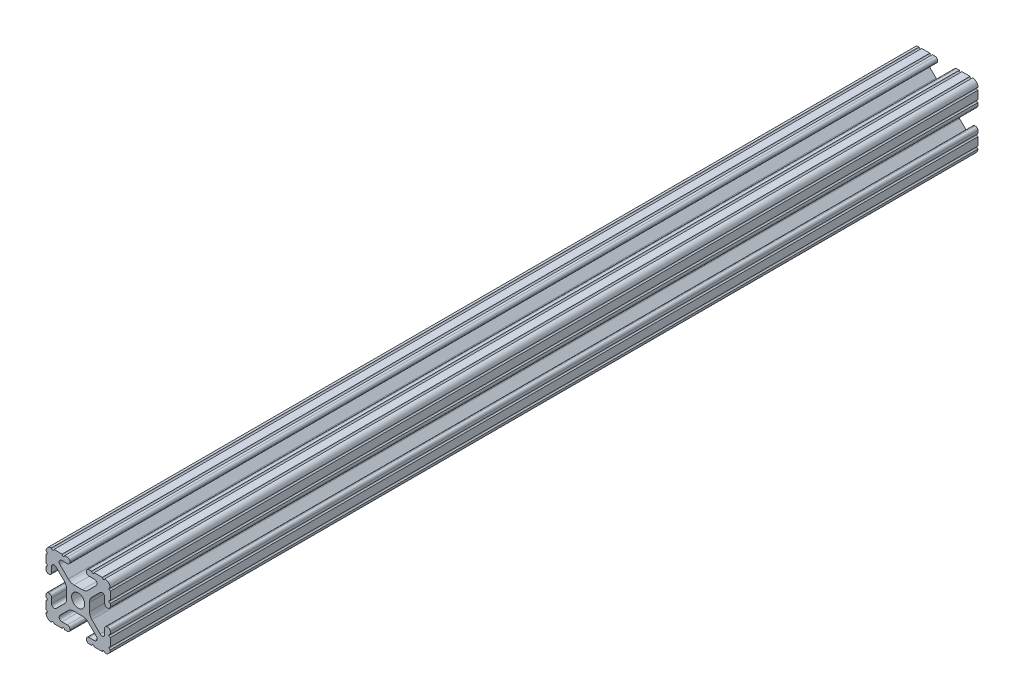
SolidWorks part; units mm, degrees
ref_plane "Front Plane" through (0, 0, 0) normal (0, 0, 1) x (1, 0, 0)
ref_plane "Top Plane" through (0, 0, 0) normal (0, 1, 0) x (1, 0, 0)
ref_plane "Right Plane" through (0, 0, 0) normal (1, 0, 0) x (0, 0, -1)
sketch "Sketch1" plane through (0, 0, 0) normal (0, 0, 1) x (1, 0, 0)
  line L88 (-7.1797, -8.6452) -> (-3.9523, -5.4237)
  line L89 (-1.7093, -4.4958) -> (1.7093, -4.4958)
  line L90 (3.9523, -5.4237) -> (7.1797, -8.6452)
  line L91 (6.4164, -10.4902) -> (4.2875, -10.4902)
  line L92 (3.2385, -11.5392) -> (3.2385, -11.651)
  line L93 (4.2875, -12.7) -> (5.3171, -12.7)
  line L94 (6.3331, -12.7) -> (9.5504, -12.7)
  line L95 (12.7, -9.5504) -> (12.7, -6.3331)
  line L96 (12.7, -5.3171) -> (12.7, -4.2875)
  line L97 (11.651, -3.2385) -> (11.5392, -3.2385)
  line L98 (10.4902, -4.2875) -> (10.4902, -6.4021)
  line L99 (8.7371, -7.1294) -> (5.441, -3.8408)
  line L100 (4.5085, -1.5932) -> (4.5085, 1.5932)
  line L101 (5.441, 3.8408) -> (8.7371, 7.1294)
  line L102 (10.4902, 6.4021) -> (10.4902, 4.2875)
  line L103 (11.5392, 3.2385) -> (11.651, 3.2385)
  line L104 (12.7, 4.2875) -> (12.7, 5.3171)
  line L105 (12.7, 6.3331) -> (12.7, 9.5504)
  line L106 (9.5504, 12.7) -> (6.3331, 12.7)
  line L107 (5.3171, 12.7) -> (4.2875, 12.7)
  line L108 (3.2385, 11.651) -> (3.2385, 11.5392)
  line L109 (4.2875, 10.4902) -> (6.4768, 10.4902)
  line L110 (7.207, 8.7244) -> (3.8983, 5.4232)
  line L111 (1.6558, 4.4958) -> (-1.6558, 4.4958)
  line L112 (-3.8983, 5.4232) -> (-7.207, 8.7244)
  line L113 (-6.4768, 10.4902) -> (-4.2875, 10.4902)
  line L114 (-3.2385, 11.5392) -> (-3.2385, 11.651)
  line L115 (-4.2875, 12.7) -> (-5.3171, 12.7)
  line L116 (-6.3331, 12.7) -> (-9.5504, 12.7)
  line L117 (-12.7, 9.5504) -> (-12.7, 6.3331)
  line L118 (-12.7, 5.3171) -> (-12.7, 4.2875)
  line L119 (-11.651, 3.2385) -> (-11.5392, 3.2385)
  line L120 (-10.4902, 4.2875) -> (-10.4902, 6.4021)
  line L121 (-8.7371, 7.1294) -> (-5.441, 3.8408)
  line L122 (-4.5085, 1.5932) -> (-4.5085, -1.5932)
  line L123 (-5.441, -3.8408) -> (-8.7371, -7.1294)
  line L124 (-10.4902, -6.4021) -> (-10.4902, -4.2875)
  line L125 (-11.5392, -3.2385) -> (-11.651, -3.2385)
  line L126 (-12.7, -4.2875) -> (-12.7, -5.3171)
  line L127 (-12.7, -6.3331) -> (-12.7, -9.5504)
  line L128 (-9.5504, -12.7) -> (-6.3331, -12.7)
  line L129 (-5.3171, -12.7) -> (-4.2875, -12.7)
  line L130 (-3.2385, -11.651) -> (-3.2385, -11.5392)
  line L131 (-4.2875, -10.4902) -> (-6.4164, -10.4902)
  circle A1 centre (0, 0) radius 2.6035
  arc A104 (-7.1797, -8.6452) -> (-6.4164, -10.4902) centre (-6.4164, -9.4098) ccw
  arc A105 (-1.7093, -4.4958) -> (-3.9523, -5.4237) centre (-1.7093, -7.6708) ccw
  arc A106 (3.9523, -5.4237) -> (1.7093, -4.4958) centre (1.7093, -7.6708) ccw
  arc A107 (6.4164, -10.4902) -> (7.1797, -8.6452) centre (6.4164, -9.4098) ccw
  arc A108 (4.2875, -10.4902) -> (3.2385, -11.5392) centre (4.2875, -11.5392) ccw
  arc A109 (3.2385, -11.651) -> (4.2875, -12.7) centre (4.2875, -11.651) ccw
  arc A110 (6.3331, -12.7) -> (5.3171, -12.7) centre (5.8251, -12.7) ccw
  arc A111 (10.5664, -12.6998) -> (9.5504, -12.7) centre (10.0584, -12.7) ccw
  arc A112 (10.5664, -12.6998) -> (12.6998, -10.5664) centre (10.5918, -10.5918) ccw
  arc A113 (12.7, -9.5504) -> (12.6998, -10.5664) centre (12.7, -10.0584) ccw
  arc A114 (12.7, -5.3171) -> (12.7, -6.3331) centre (12.7, -5.8251) ccw
  arc A115 (12.7, -4.2875) -> (11.651, -3.2385) centre (11.651, -4.2875) ccw
  arc A116 (11.5392, -3.2385) -> (10.4902, -4.2875) centre (11.5392, -4.2875) ccw
  arc A117 (8.7371, -7.1294) -> (10.4902, -6.4021) centre (9.4628, -6.4021) ccw
  arc A118 (4.5085, -1.5932) -> (5.441, -3.8408) centre (7.6835, -1.5932) ccw
  arc A119 (5.441, 3.8408) -> (4.5085, 1.5932) centre (7.6835, 1.5932) ccw
  arc A120 (10.4902, 6.4021) -> (8.7371, 7.1294) centre (9.4628, 6.4021) ccw
  arc A121 (10.4902, 4.2875) -> (11.5392, 3.2385) centre (11.5392, 4.2875) ccw
  arc A122 (11.651, 3.2385) -> (12.7, 4.2875) centre (11.651, 4.2875) ccw
  arc A123 (12.7, 6.3331) -> (12.7, 5.3171) centre (12.7, 5.8251) ccw
  arc A124 (12.6998, 10.5664) -> (12.7, 9.5504) centre (12.7, 10.0584) ccw
  arc A125 (12.6998, 10.5664) -> (10.5664, 12.6998) centre (10.5918, 10.5918) ccw
  arc A126 (9.5504, 12.7) -> (10.5664, 12.6998) centre (10.0584, 12.7) ccw
  arc A127 (5.3171, 12.7) -> (6.3331, 12.7) centre (5.8251, 12.7) ccw
  arc A128 (4.2875, 12.7) -> (3.2385, 11.651) centre (4.2875, 11.651) ccw
  arc A129 (3.2385, 11.5392) -> (4.2875, 10.4902) centre (4.2875, 11.5392) ccw
  arc A130 (7.207, 8.7244) -> (6.4768, 10.4902) centre (6.4768, 9.4563) ccw
  arc A131 (1.6558, 4.4958) -> (3.8983, 5.4232) centre (1.6558, 7.6708) ccw
  arc A132 (-3.8983, 5.4232) -> (-1.6558, 4.4958) centre (-1.6558, 7.6708) ccw
  arc A133 (-6.4768, 10.4902) -> (-7.207, 8.7244) centre (-6.4768, 9.4563) ccw
  arc A134 (-4.2875, 10.4902) -> (-3.2385, 11.5392) centre (-4.2875, 11.5392) ccw
  arc A135 (-3.2385, 11.651) -> (-4.2875, 12.7) centre (-4.2875, 11.651) ccw
  arc A136 (-6.3331, 12.7) -> (-5.3171, 12.7) centre (-5.8251, 12.7) ccw
  arc A137 (-10.5664, 12.6998) -> (-9.5504, 12.7) centre (-10.0584, 12.7) ccw
  arc A138 (-10.5664, 12.6998) -> (-12.6998, 10.5664) centre (-10.5918, 10.5918) ccw
  arc A139 (-12.7, 9.5504) -> (-12.6998, 10.5664) centre (-12.7, 10.0584) ccw
  arc A140 (-12.7, 5.3171) -> (-12.7, 6.3331) centre (-12.7, 5.8251) ccw
  arc A141 (-12.7, 4.2875) -> (-11.651, 3.2385) centre (-11.651, 4.2875) ccw
  arc A142 (-11.5392, 3.2385) -> (-10.4902, 4.2875) centre (-11.5392, 4.2875) ccw
  arc A143 (-8.7371, 7.1294) -> (-10.4902, 6.4021) centre (-9.4628, 6.4021) ccw
  arc A144 (-4.5085, 1.5932) -> (-5.441, 3.8408) centre (-7.6835, 1.5932) ccw
  arc A145 (-5.441, -3.8408) -> (-4.5085, -1.5932) centre (-7.6835, -1.5932) ccw
  arc A146 (-10.4902, -6.4021) -> (-8.7371, -7.1294) centre (-9.4628, -6.4021) ccw
  arc A147 (-10.4902, -4.2875) -> (-11.5392, -3.2385) centre (-11.5392, -4.2875) ccw
  arc A148 (-11.651, -3.2385) -> (-12.7, -4.2875) centre (-11.651, -4.2875) ccw
  arc A149 (-12.7, -6.3331) -> (-12.7, -5.3171) centre (-12.7, -5.8251) ccw
  arc A150 (-12.6998, -10.5664) -> (-12.7, -9.5504) centre (-12.7, -10.0584) ccw
  arc A151 (-12.6998, -10.5664) -> (-10.5664, -12.6998) centre (-10.5918, -10.5918) ccw
  arc A152 (-9.5504, -12.7) -> (-10.5664, -12.6998) centre (-10.0584, -12.7) ccw
  arc A153 (-5.3171, -12.7) -> (-6.3331, -12.7) centre (-5.8251, -12.7) ccw
  arc A154 (-4.2875, -12.7) -> (-3.2385, -11.651) centre (-4.2875, -11.651) ccw
  arc A155 (-3.2385, -11.5392) -> (-4.2875, -10.4902) centre (-4.2875, -11.5392) ccw
extrude "Boss-Extrude1" add sketch "Sketch1" along normal mid plane 431.8
ref_plane "Plane1" through (0, 0, 0) normal (0, 1, 0) x (1, 0, 0)
ref_plane "Plane2" through (0, 0, 0) normal (-1, 0, 0) x (0, 0, 1)
sketch "Sketch2" plane through (0, 0, -215.9) normal (0, 0, -1) x (-1, 0, 0)
  line L44 (6.4164, -10.4902) -> (4.2875, -10.4902)
  line L45 (3.2385, -11.5392) -> (3.2385, -11.651)
  line L46 (4.2875, -12.7) -> (5.3171, -12.7)
  line L47 (6.3331, -12.7) -> (9.5504, -12.7)
  line L48 (12.7, -9.5504) -> (12.7, -6.3331)
  line L49 (12.7, -5.3171) -> (12.7, -4.2875)
  line L50 (11.651, -3.2385) -> (11.5392, -3.2385)
  line L51 (10.4902, -4.2875) -> (10.4902, -6.4021)
  line L52 (8.7371, -7.1294) -> (5.441, -3.8408)
  line L53 (4.5085, -1.5932) -> (4.5085, 1.5932)
  line L54 (5.441, 3.8408) -> (8.7371, 7.1294)
  line L55 (10.4902, 6.4021) -> (10.4902, 4.2875)
  line L56 (11.5392, 3.2385) -> (11.651, 3.2385)
  line L57 (12.7, 4.2875) -> (12.7, 5.3171)
  line L58 (12.7, 6.3331) -> (12.7, 9.5504)
  line L59 (9.5504, 12.7) -> (6.3331, 12.7)
  line L60 (5.3171, 12.7) -> (4.2875, 12.7)
  line L61 (3.2385, 11.651) -> (3.2385, 11.5392)
  line L62 (4.2875, 10.4902) -> (6.4768, 10.4902)
  line L63 (7.207, 8.7244) -> (3.8983, 5.4232)
  line L64 (1.6558, 4.4958) -> (-1.6558, 4.4958)
  line L65 (-3.8983, 5.4232) -> (-7.207, 8.7244)
  line L66 (-6.4768, 10.4902) -> (-4.2875, 10.4902)
  line L67 (-3.2385, 11.5392) -> (-3.2385, 11.651)
  line L68 (-4.2875, 12.7) -> (-5.3171, 12.7)
  line L69 (-6.3331, 12.7) -> (-9.5504, 12.7)
  line L70 (-12.7, 9.5504) -> (-12.7, 6.3331)
  line L71 (-12.7, 5.3171) -> (-12.7, 4.2875)
  line L72 (-11.651, 3.2385) -> (-11.5392, 3.2385)
  line L73 (-10.4902, 4.2875) -> (-10.4902, 6.4021)
  line L74 (-8.7371, 7.1294) -> (-5.441, 3.8408)
  line L75 (-4.5085, 1.5932) -> (-4.5085, -1.5932)
  line L76 (-5.441, -3.8408) -> (-8.7371, -7.1294)
  line L77 (-10.4902, -6.4021) -> (-10.4902, -4.2875)
  line L78 (-11.5392, -3.2385) -> (-11.651, -3.2385)
  line L79 (-12.7, -4.2875) -> (-12.7, -5.3171)
  line L80 (-12.7, -6.3331) -> (-12.7, -9.5504)
  line L81 (-9.5504, -12.7) -> (-6.3331, -12.7)
  line L82 (-5.3171, -12.7) -> (-4.2875, -12.7)
  line L83 (-3.2385, -11.651) -> (-3.2385, -11.5392)
  line L84 (-4.2875, -10.4902) -> (-6.4164, -10.4902)
  line L85 (-7.1797, -8.6452) -> (-3.9523, -5.4237)
  line L86 (-1.7093, -4.4958) -> (1.7093, -4.4958)
  line L87 (3.9523, -5.4237) -> (7.1797, -8.6452)
  line L88 (6.4164, -10.4902) -> (4.2875, -10.4902)
  line L89 (3.2385, -11.5392) -> (3.2385, -11.651)
  line L90 (4.2875, -12.7) -> (5.3171, -12.7)
  line L91 (6.3331, -12.7) -> (9.5504, -12.7)
  line L92 (12.7, -9.5504) -> (12.7, -6.3331)
  line L93 (12.7, -5.3171) -> (12.7, -4.2875)
  line L94 (11.651, -3.2385) -> (11.5392, -3.2385)
  line L95 (10.4902, -4.2875) -> (10.4902, -6.4021)
  line L96 (8.7371, -7.1294) -> (5.441, -3.8408)
  line L97 (4.5085, -1.5932) -> (4.5085, 1.5932)
  line L98 (5.441, 3.8408) -> (8.7371, 7.1294)
  line L99 (10.4902, 6.4021) -> (10.4902, 4.2875)
  line L100 (11.5392, 3.2385) -> (11.651, 3.2385)
  line L101 (12.7, 4.2875) -> (12.7, 5.3171)
  line L102 (12.7, 6.3331) -> (12.7, 9.5504)
  line L103 (9.5504, 12.7) -> (6.3331, 12.7)
  line L104 (5.3171, 12.7) -> (4.2875, 12.7)
  line L105 (3.2385, 11.651) -> (3.2385, 11.5392)
  line L106 (4.2875, 10.4902) -> (6.4768, 10.4902)
  line L107 (7.207, 8.7244) -> (3.8983, 5.4232)
  line L108 (1.6558, 4.4958) -> (-1.6558, 4.4958)
  line L109 (-3.8983, 5.4232) -> (-7.207, 8.7244)
  line L110 (-6.4768, 10.4902) -> (-4.2875, 10.4902)
  line L111 (-3.2385, 11.5392) -> (-3.2385, 11.651)
  line L112 (-4.2875, 12.7) -> (-5.3171, 12.7)
  line L113 (-6.3331, 12.7) -> (-9.5504, 12.7)
  line L114 (-12.7, 9.5504) -> (-12.7, 6.3331)
  line L115 (-12.7, 5.3171) -> (-12.7, 4.2875)
  line L116 (-11.651, 3.2385) -> (-11.5392, 3.2385)
  line L117 (-10.4902, 4.2875) -> (-10.4902, 6.4021)
  line L118 (-8.7371, 7.1294) -> (-5.441, 3.8408)
  line L119 (-4.5085, 1.5932) -> (-4.5085, -1.5932)
  line L120 (-5.441, -3.8408) -> (-8.7371, -7.1294)
  line L121 (-10.4902, -6.4021) -> (-10.4902, -4.2875)
  line L122 (-11.5392, -3.2385) -> (-11.651, -3.2385)
  line L123 (-12.7, -4.2875) -> (-12.7, -5.3171)
  line L124 (-12.7, -6.3331) -> (-12.7, -9.5504)
  line L125 (-9.5504, -12.7) -> (-6.3331, -12.7)
  line L126 (-5.3171, -12.7) -> (-4.2875, -12.7)
  line L127 (-3.2385, -11.651) -> (-3.2385, -11.5392)
  line L128 (-4.2875, -10.4902) -> (-6.4164, -10.4902)
  line L129 (-7.1797, -8.6452) -> (-3.9523, -5.4237)
  line L130 (-1.7093, -4.4958) -> (1.7093, -4.4958)
  line L131 (3.9523, -5.4237) -> (7.1797, -8.6452)
  arc A52 (6.4164, -10.4902) -> (7.1797, -8.6452) centre (6.4164, -9.4098) ccw
  arc A53 (4.2875, -10.4902) -> (3.2385, -11.5392) centre (4.2875, -11.5392) ccw
  arc A54 (3.2385, -11.651) -> (4.2875, -12.7) centre (4.2875, -11.651) ccw
  arc A55 (6.3331, -12.7) -> (5.3171, -12.7) centre (5.8251, -12.7) ccw
  arc A56 (10.5664, -12.6998) -> (9.5504, -12.7) centre (10.0584, -12.7) ccw
  arc A57 (10.5664, -12.6998) -> (12.6998, -10.5664) centre (10.5918, -10.5918) ccw
  arc A58 (12.7, -9.5504) -> (12.6998, -10.5664) centre (12.7, -10.0584) ccw
  arc A59 (12.7, -5.3171) -> (12.7, -6.3331) centre (12.7, -5.8251) ccw
  arc A60 (12.7, -4.2875) -> (11.651, -3.2385) centre (11.651, -4.2875) ccw
  arc A61 (11.5392, -3.2385) -> (10.4902, -4.2875) centre (11.5392, -4.2875) ccw
  arc A62 (8.7371, -7.1294) -> (10.4902, -6.4021) centre (9.4628, -6.4021) ccw
  arc A63 (4.5085, -1.5932) -> (5.441, -3.8408) centre (7.6835, -1.5932) ccw
  arc A64 (5.441, 3.8408) -> (4.5085, 1.5932) centre (7.6835, 1.5932) ccw
  arc A65 (10.4902, 6.4021) -> (8.7371, 7.1294) centre (9.4628, 6.4021) ccw
  arc A66 (10.4902, 4.2875) -> (11.5392, 3.2385) centre (11.5392, 4.2875) ccw
  arc A67 (11.651, 3.2385) -> (12.7, 4.2875) centre (11.651, 4.2875) ccw
  arc A68 (12.7, 6.3331) -> (12.7, 5.3171) centre (12.7, 5.8251) ccw
  arc A69 (12.6998, 10.5664) -> (12.7, 9.5504) centre (12.7, 10.0584) ccw
  arc A70 (12.6998, 10.5664) -> (10.5664, 12.6998) centre (10.5918, 10.5918) ccw
  arc A71 (9.5504, 12.7) -> (10.5664, 12.6998) centre (10.0584, 12.7) ccw
  arc A72 (5.3171, 12.7) -> (6.3331, 12.7) centre (5.8251, 12.7) ccw
  arc A73 (4.2875, 12.7) -> (3.2385, 11.651) centre (4.2875, 11.651) ccw
  arc A74 (3.2385, 11.5392) -> (4.2875, 10.4902) centre (4.2875, 11.5392) ccw
  arc A75 (7.207, 8.7244) -> (6.4768, 10.4902) centre (6.4768, 9.4563) ccw
  arc A76 (1.6558, 4.4958) -> (3.8983, 5.4232) centre (1.6558, 7.6708) ccw
  arc A77 (-3.8983, 5.4232) -> (-1.6558, 4.4958) centre (-1.6558, 7.6708) ccw
  arc A78 (-6.4768, 10.4902) -> (-7.207, 8.7244) centre (-6.4768, 9.4563) ccw
  arc A79 (-4.2875, 10.4902) -> (-3.2385, 11.5392) centre (-4.2875, 11.5392) ccw
  arc A80 (-3.2385, 11.651) -> (-4.2875, 12.7) centre (-4.2875, 11.651) ccw
  arc A81 (-6.3331, 12.7) -> (-5.3171, 12.7) centre (-5.8251, 12.7) ccw
  arc A82 (-10.5664, 12.6998) -> (-9.5504, 12.7) centre (-10.0584, 12.7) ccw
  arc A83 (-10.5664, 12.6998) -> (-12.6998, 10.5664) centre (-10.5918, 10.5918) ccw
  arc A84 (-12.7, 9.5504) -> (-12.6998, 10.5664) centre (-12.7, 10.0584) ccw
  arc A85 (-12.7, 5.3171) -> (-12.7, 6.3331) centre (-12.7, 5.8251) ccw
  arc A86 (-12.7, 4.2875) -> (-11.651, 3.2385) centre (-11.651, 4.2875) ccw
  arc A87 (-11.5392, 3.2385) -> (-10.4902, 4.2875) centre (-11.5392, 4.2875) ccw
  arc A88 (-8.7371, 7.1294) -> (-10.4902, 6.4021) centre (-9.4628, 6.4021) ccw
  arc A89 (-4.5085, 1.5932) -> (-5.441, 3.8408) centre (-7.6835, 1.5932) ccw
  arc A90 (-5.441, -3.8408) -> (-4.5085, -1.5932) centre (-7.6835, -1.5932) ccw
  arc A91 (-10.4902, -6.4021) -> (-8.7371, -7.1294) centre (-9.4628, -6.4021) ccw
  arc A92 (-10.4902, -4.2875) -> (-11.5392, -3.2385) centre (-11.5392, -4.2875) ccw
  arc A93 (-11.651, -3.2385) -> (-12.7, -4.2875) centre (-11.651, -4.2875) ccw
  arc A94 (-12.7, -6.3331) -> (-12.7, -5.3171) centre (-12.7, -5.8251) ccw
  arc A95 (-12.6998, -10.5664) -> (-12.7, -9.5504) centre (-12.7, -10.0584) ccw
  arc A96 (-12.6998, -10.5664) -> (-10.5664, -12.6998) centre (-10.5918, -10.5918) ccw
  arc A97 (-9.5504, -12.7) -> (-10.5664, -12.6998) centre (-10.0584, -12.7) ccw
  arc A98 (-5.3171, -12.7) -> (-6.3331, -12.7) centre (-5.8251, -12.7) ccw
  arc A99 (-4.2875, -12.7) -> (-3.2385, -11.651) centre (-4.2875, -11.651) ccw
  arc A100 (-3.2385, -11.5392) -> (-4.2875, -10.4902) centre (-4.2875, -11.5392) ccw
  arc A101 (-7.1797, -8.6452) -> (-6.4164, -10.4902) centre (-6.4164, -9.4098) ccw
  arc A102 (-1.7093, -4.4958) -> (-3.9523, -5.4237) centre (-1.7093, -7.6708) ccw
  arc A103 (3.9523, -5.4237) -> (1.7093, -4.4958) centre (1.7093, -7.6708) ccw
  arc A104 (6.4164, -10.4902) -> (7.1797, -8.6452) centre (6.4164, -9.4098) ccw
  arc A105 (4.2875, -10.4902) -> (3.2385, -11.5392) centre (4.2875, -11.5392) ccw
  arc A106 (3.2385, -11.651) -> (4.2875, -12.7) centre (4.2875, -11.651) ccw
  arc A107 (6.3331, -12.7) -> (5.3171, -12.7) centre (5.8251, -12.7) ccw
  arc A108 (10.5664, -12.6998) -> (9.5504, -12.7) centre (10.0584, -12.7) ccw
  arc A109 (10.5664, -12.6998) -> (12.6998, -10.5664) centre (10.5918, -10.5918) ccw
  arc A110 (12.7, -9.5504) -> (12.6998, -10.5664) centre (12.7, -10.0584) ccw
  arc A111 (12.7, -5.3171) -> (12.7, -6.3331) centre (12.7, -5.8251) ccw
  arc A112 (12.7, -4.2875) -> (11.651, -3.2385) centre (11.651, -4.2875) ccw
  arc A113 (11.5392, -3.2385) -> (10.4902, -4.2875) centre (11.5392, -4.2875) ccw
  arc A114 (8.7371, -7.1294) -> (10.4902, -6.4021) centre (9.4628, -6.4021) ccw
  arc A115 (4.5085, -1.5932) -> (5.441, -3.8408) centre (7.6835, -1.5932) ccw
  arc A116 (5.441, 3.8408) -> (4.5085, 1.5932) centre (7.6835, 1.5932) ccw
  arc A117 (10.4902, 6.4021) -> (8.7371, 7.1294) centre (9.4628, 6.4021) ccw
  arc A118 (10.4902, 4.2875) -> (11.5392, 3.2385) centre (11.5392, 4.2875) ccw
  arc A119 (11.651, 3.2385) -> (12.7, 4.2875) centre (11.651, 4.2875) ccw
  arc A120 (12.7, 6.3331) -> (12.7, 5.3171) centre (12.7, 5.8251) ccw
  arc A121 (12.6998, 10.5664) -> (12.7, 9.5504) centre (12.7, 10.0584) ccw
  arc A122 (12.6998, 10.5664) -> (10.5664, 12.6998) centre (10.5918, 10.5918) ccw
  arc A123 (9.5504, 12.7) -> (10.5664, 12.6998) centre (10.0584, 12.7) ccw
  arc A124 (5.3171, 12.7) -> (6.3331, 12.7) centre (5.8251, 12.7) ccw
  arc A125 (4.2875, 12.7) -> (3.2385, 11.651) centre (4.2875, 11.651) ccw
  arc A126 (3.2385, 11.5392) -> (4.2875, 10.4902) centre (4.2875, 11.5392) ccw
  arc A127 (7.207, 8.7244) -> (6.4768, 10.4902) centre (6.4768, 9.4563) ccw
  arc A128 (1.6558, 4.4958) -> (3.8983, 5.4232) centre (1.6558, 7.6708) ccw
  arc A129 (-3.8983, 5.4232) -> (-1.6558, 4.4958) centre (-1.6558, 7.6708) ccw
  arc A130 (-6.4768, 10.4902) -> (-7.207, 8.7244) centre (-6.4768, 9.4563) ccw
  arc A131 (-4.2875, 10.4902) -> (-3.2385, 11.5392) centre (-4.2875, 11.5392) ccw
  arc A132 (-3.2385, 11.651) -> (-4.2875, 12.7) centre (-4.2875, 11.651) ccw
  arc A133 (-6.3331, 12.7) -> (-5.3171, 12.7) centre (-5.8251, 12.7) ccw
  arc A134 (-10.5664, 12.6998) -> (-9.5504, 12.7) centre (-10.0584, 12.7) ccw
  arc A135 (-10.5664, 12.6998) -> (-12.6998, 10.5664) centre (-10.5918, 10.5918) ccw
  arc A136 (-12.7, 9.5504) -> (-12.6998, 10.5664) centre (-12.7, 10.0584) ccw
  arc A137 (-12.7, 5.3171) -> (-12.7, 6.3331) centre (-12.7, 5.8251) ccw
  arc A138 (-12.7, 4.2875) -> (-11.651, 3.2385) centre (-11.651, 4.2875) ccw
  arc A139 (-11.5392, 3.2385) -> (-10.4902, 4.2875) centre (-11.5392, 4.2875) ccw
  arc A140 (-8.7371, 7.1294) -> (-10.4902, 6.4021) centre (-9.4628, 6.4021) ccw
  arc A141 (-4.5085, 1.5932) -> (-5.441, 3.8408) centre (-7.6835, 1.5932) ccw
  arc A142 (-5.441, -3.8408) -> (-4.5085, -1.5932) centre (-7.6835, -1.5932) ccw
  arc A143 (-10.4902, -6.4021) -> (-8.7371, -7.1294) centre (-9.4628, -6.4021) ccw
  arc A144 (-10.4902, -4.2875) -> (-11.5392, -3.2385) centre (-11.5392, -4.2875) ccw
  arc A145 (-11.651, -3.2385) -> (-12.7, -4.2875) centre (-11.651, -4.2875) ccw
  arc A146 (-12.7, -6.3331) -> (-12.7, -5.3171) centre (-12.7, -5.8251) ccw
  arc A147 (-12.6998, -10.5664) -> (-12.7, -9.5504) centre (-12.7, -10.0584) ccw
  arc A148 (-12.6998, -10.5664) -> (-10.5664, -12.6998) centre (-10.5918, -10.5918) ccw
  arc A149 (-9.5504, -12.7) -> (-10.5664, -12.6998) centre (-10.0584, -12.7) ccw
  arc A150 (-5.3171, -12.7) -> (-6.3331, -12.7) centre (-5.8251, -12.7) ccw
  arc A151 (-4.2875, -12.7) -> (-3.2385, -11.651) centre (-4.2875, -11.651) ccw
  arc A152 (-3.2385, -11.5392) -> (-4.2875, -10.4902) centre (-4.2875, -11.5392) ccw
  arc A153 (-7.1797, -8.6452) -> (-6.4164, -10.4902) centre (-6.4164, -9.4098) ccw
  arc A154 (-1.7093, -4.4958) -> (-3.9523, -5.4237) centre (-1.7093, -7.6708) ccw
  arc A155 (3.9523, -5.4237) -> (1.7093, -4.4958) centre (1.7093, -7.6708) ccw
  dimension "D1" = 0
extrude "Cut-Extrude1" cut sketch "Sketch2" against normal up to surface (88.9 mm away) up to face at (0, 0.0014, -215.9)
